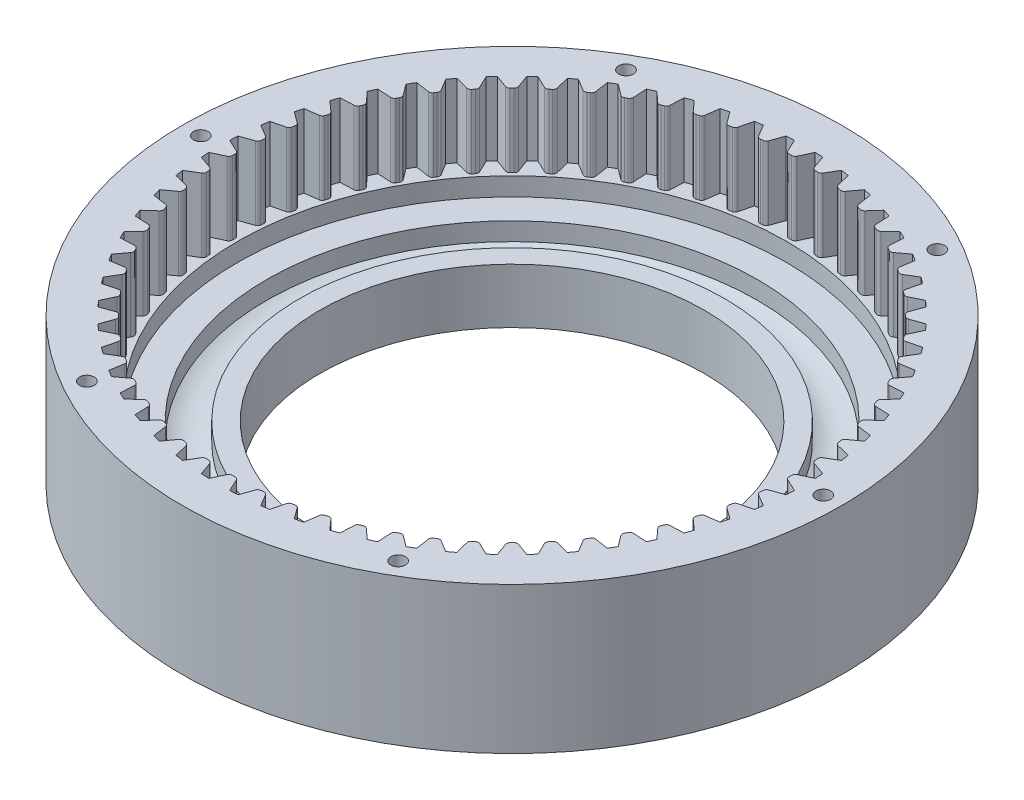
SolidWorks part; units mm, degrees
ref_plane "Front Plane" through (0, 0, 0) normal (0, 0, 1) x (1, 0, 0)
ref_plane "Top Plane" through (0, 0, 0) normal (0, 1, 0) x (1, 0, 0)
ref_plane "Right Plane" through (0, 0, 0) normal (1, 0, 0) x (0, 0, -1)
sketch "Sketch1" plane through (0, 0, 0) normal (0, 0, 1) x (1, 0, 0)
  line L0 (0, 0) -> (0, 36.773) construction
  line L2 (-90, 0) -> (-90, 40)
  line L3 (-90, 40) -> (-80, 40)
  line L4 (-80, 40) -> (-80, 20)
  line L5 (-75, 15) -> (-67, 15)
  line L6 (-67, 15) -> (-67, 10.0697)
  line L7 (-58, 10.0697) -> (-58, 15)
  line L8 (-58, 15) -> (-52.5, 15)
  line L10 (-67, 15) -> (-58, 15) construction
  line L12 (-52.5, 15) -> (-52.5, 0)
  line L16 (-52.5, 0) -> (-90, 0)
  line L18 (-80, 20) -> (-75, 20)
  line L19 (-75, 20) -> (-75, 15)
  arc A0 (-67, 10.0697) -> (-58, 10.0697) centre (-62.5, 19) ccw
  point P2 (-53.1214, 0)
  point P14 (-62.5, 15)
  point P16 (-62.5, 9)
  dimension "D5" = 10
  dimension "D2" = 150
  dimension "D3" = 40
  dimension "D4" = 9
  dimension "D6" = 6
  dimension "D7" = 160
  dimension "D8" = 15
  dimension "D9" = 105
  dimension "D12" = 20
  dimension "D13" = 180
  dimension "D14" = 125
revolve "Revolve1" add sketch "Sketch1" angle 360 about L0
sketch "Sketch2" plane through (0, 20, 0) normal (0, 1, 0) x (1, 0, 0)
  line L0 (-79.9495, 2.8417) -> (-76.5774, 1.2692)
  line L1 (-76.5774, -1.2692) -> (-79.9495, -2.8417)
  line L2 (-76, -0.3629) -> (-76, 0.3629)
  circle A1 centre (0, 0) radius 80 construction
  circle A2 centre (0, 0) radius 80 construction
  arc A4 (-79.9495, 2.8417) -> (-79.9495, -2.8417) centre (0, 0) ccw
  arc A5 (-76, -0.3629) -> (-76.5774, -1.2692) centre (-77, -0.3629) cw
  arc A6 (-76.5774, 1.2692) -> (-76, 0.3629) centre (-77, 0.3629) cw
  point P9 (-76, -1)
  point P11 (-80, 0)
  point P15 (-76, 1)
  dimension "D1" = 4
  dimension "D4" = 1
  dimension "D2" = 50
  dimension "D3" = 2
extrude "Boss-Extrude1" add sketch "Sketch2" along normal up to surface (20 mm away) up to face at (0, 40, -90)
pattern_circular "CirPattern1" count 64 over 360 about axis through (0, 0, 0) along (0, -1, 0) of "Boss-Extrude1" reverse direction yes
sketch "Sketch3" plane through (0, 40, 0) normal (0, 1, 0) x (1, 0, 0)
  circle A0 centre (-85, 0) radius 2
  dimension "D2" = 4
  dimension "D1" = 85
extrude "Cut-Extrude1" cut sketch "Sketch3" against normal blind 15
pattern_circular "CirPattern2" count 6 over 360 about axis through (0, 0, 0) along (0, -1, 0) of "Cut-Extrude1" reverse direction yes
sketch "Sketch4" plane through (0, 0, 0) normal (0, -1, 0) x (-1, 0, 0)
  circle A0 centre (78, 0) radius 4
  point P2 (0, 0)
  dimension "D1" = 8
  dimension "D2" = 78
extrude "Cut-Extrude2" cut sketch "Sketch4" against normal blind 12
pattern_circular "CirPattern3" count 4 over 360 about axis through (0, 0, 0) along (0, -1, 0) of "Cut-Extrude2" reverse direction yes
